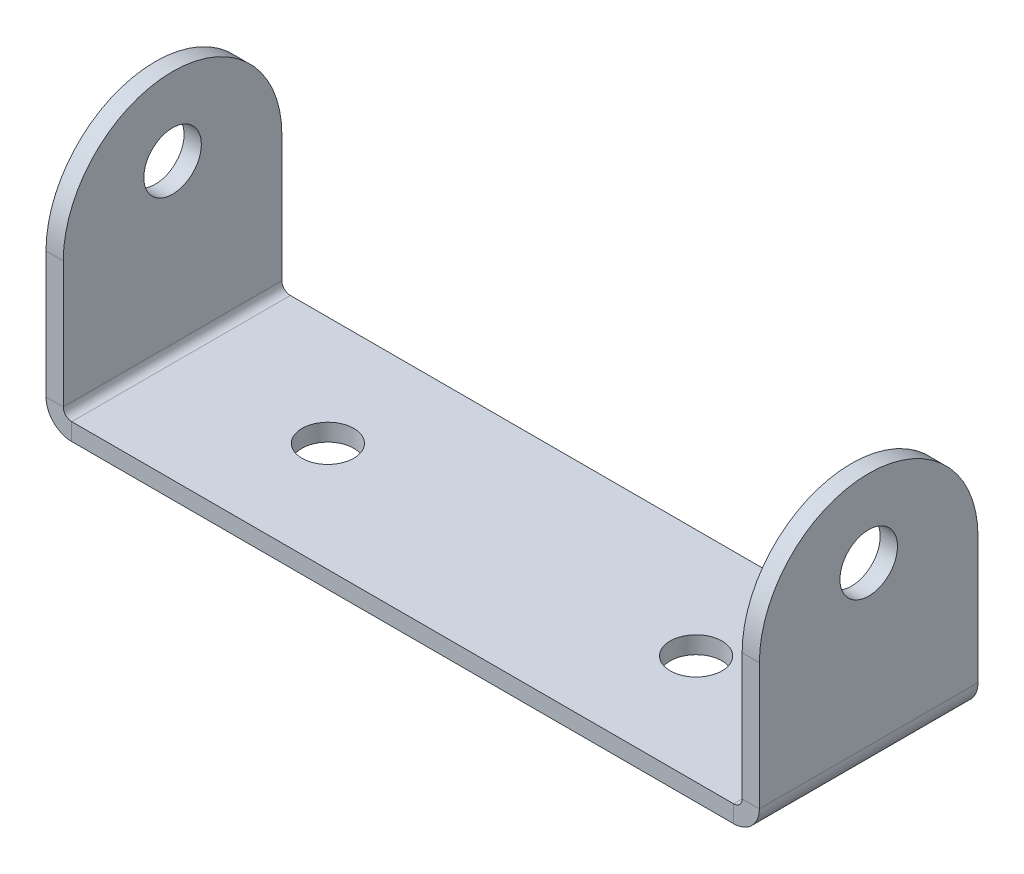
SolidWorks part; units mm, degrees
note: The reader was unsure of these and kept them because the rebuilt part matched: flange length of "Edge-Flange1", "Edge-Flange2".
ref_plane "Front Plane" through (0, 0, 0) normal (0, 0, 1) x (1, 0, 0)
ref_plane "Top Plane" through (0, 0, 0) normal (0, 1, 0) x (1, 0, 0)
ref_plane "Right Plane" through (0, 0, 0) normal (1, 0, 0) x (0, 0, -1)
sketch "Sketch1" plane through (0, 0, 0) normal (0, 1, 0) x (1, 0, 0)
  line L0 (0, 9.5) -> (15, 9.5) construction
  line L1 (0, 0) -> (62, 0)
  line L2 (0, 0) -> (0, 19)
  line L3 (0, 19) -> (62, 19)
  line L4 (62, 0) -> (62, 19)
  line L5 (62, 9.5) -> (47, 9.5) construction
  circle A0 centre (15, 9.5) radius 2.25
  circle A1 centre (47, 9.5) radius 2.25
  dimension "D5" = 4.5
  dimension "D6" = 4.5
  dimension "D1" = 19
  dimension "D2" = 62
  dimension "D3" = 15
  dimension "D4" = 15
base flange "Base-Flange1" sketch "Sketch1" thickness 1.5 reverse thickness direction no parameters "D1"=0.7366
edge flange "Edge-Flange1" sketch "Sketch8" flange angle 90 flange length 23 flange position material inside bend radius 0.7366 thickness 1.5 relief rectangular parameters "D6"=10
sketch "Sketch8" plane through (0, 0, 0) normal (-1, 0, 0) x (0, 0, 1)
  line L2 (-19, 0) -> (-19, 21.5)
  line L3 (-19, 21.5) -> (0, 21.5)
  line L4 (0, 21.5) -> (0, 0)
  line L7 (-19, 0) -> (0, 0) construction
  line L8 (-19, 0) -> (0, 0)
bend "EdgeBend1" bend radius 0.7366 bend angle 90 parameters "D5"=1
edge flange "Edge-Flange2" sketch "Sketch11" flange angle 90 flange length 23 flange position material inside bend radius 0.7366 thickness 1.5 relief rectangular parameters "D6"=10
sketch "Sketch11" plane through (62, 0, 0) normal (1, 0, 0) x (0, 0, -1)
  line L2 (0, 0) -> (0, 21.5)
  line L3 (0, 21.5) -> (19, 21.5)
  line L4 (19, 21.5) -> (19, 0)
  line L7 (0, 0) -> (19, 0) construction
  line L8 (0, 0) -> (19, 0)
bend "EdgeBend2" bend radius 0.7366 bend angle 90 parameters "D5"=2
sketch "Sketch12" plane through (62, 0, 0) normal (1, 0, 0) x (0, 0, -1)
  line L0 (9.5, 0.7366) -> (9.5, 11.7366) construction
  line L1 (19, 0.7366) -> (0, 0.7366) construction
  line L2 (0, 21.5) -> (0, 0.7366) construction
  line L3 (19, 0.7366) -> (19, 21.5) construction
  line L4 (0, 11.7366) -> (-3.0236, 11.7366)
  line L5 (-3.0236, 11.7366) -> (-3.0236, 23.5215)
  line L6 (-3.0236, 23.5215) -> (21.6636, 23.5215)
  line L7 (21.6636, 23.5215) -> (21.6636, 11.7366)
  line L8 (21.6636, 11.7366) -> (19, 11.7366)
  line L9 (9.5, 21.5) -> (9.5, 14.5) construction
  line L10 (19, 21.5) -> (0, 21.5) construction
  arc A0 (0, 11.7366) -> (19, 11.7366) centre (9.5, 11.7366) cw
  circle A2 centre (9.5, 14.5) radius 2.5
  dimension "D2" = 7
  dimension "D1" = 11
extrude "Cut-Extrude1" cut sketch "Sketch12" against normal through all normal cut yes
sketch "Bend-Lines1" [suppressed] plane through (0, 0, 0) normal (0, 1, 0) x (1, 0, 0)
sketch "Bounding-Box1" [suppressed] plane through (0, 0, 0) normal (0, 1, 0) x (1, 0, 0)
sheet metal parameters "Sheet-Metal1" thickness 1.5 parameters "D1"=0.7366
flat pattern "Flat-Pattern1" [suppressed]
sketch "Bend-Lines2" plane through (0, 0, 0) normal (0, 1, 0) x (1, 0, 0)
sketch3d "Bounding-Box2" [suppressed]
  line L0 (-62, 19, 0) -> (0, 19, 0) construction
  line L1 (-62, 0, 0) -> (0, 0, 0) construction
  line L2 (-62, 19, 0) -> (-62, 0, 0) construction
  line L3 (0, 19, 0) -> (0, 0, 0) construction
sheet metal parameters "Sheet-Metal2" thickness 1.5 parameters "D1"=0.7366
flat pattern "Flat-Pattern1"
sketch "Bend-Lines2" plane through (0, 0, 0) normal (0, 1, 0) x (1, 0, 0)
  line L0 (1.069, 19) -> (1.069, 0) construction
  line L1 (1.069, 19) -> (1.069, 0) construction
sketch3d "Bounding-Box2" [suppressed]
  line L0 (62, 19, 0) -> (-20.8619, 19, 0) construction
  line L1 (62, 0, 0) -> (-20.8619, 0, 0) construction
  line L2 (62, 19, 0) -> (62, 0, 0) construction
  line L3 (-20.8619, 19, 0) -> (-20.8619, 0, 0) construction
bend of the flat pattern "Flatten-<EdgeBend1>1"
sheet metal parameters "Sheet-Metal3" thickness 1.5 parameters "D1"=0.7366
flat pattern "Flat-Pattern1"
sketch "Bend-Lines2" plane through (0, 0, 0) normal (0, 1, 0) x (1, 0, 0)
  line L0 (1.069, 19) -> (1.069, 0) construction
  line L1 (1.069, 19) -> (1.069, 0) construction
  line L2 (60.931, 0) -> (60.931, 19) construction
  line L3 (60.931, 0) -> (60.931, 19) construction
sketch3d "Bounding-Box2" [suppressed]
  line L0 (82.8619, 19, 0) -> (-20.8619, 19, 0) construction
  line L1 (82.8619, 0, 0) -> (-20.8619, 0, 0) construction
  line L2 (82.8619, 19, 0) -> (82.8619, 0, 0) construction
  line L3 (-20.8619, 19, 0) -> (-20.8619, 0, 0) construction
bend of the flat pattern "Flatten-<EdgeBend1>1"
bend of the flat pattern "Flatten-<EdgeBend2>1"
sheet metal parameters "Sheet-Metal4" thickness 1.5 parameters "D1"=0.7366
flat pattern "Flat-Pattern1"
sketch "Bend-Lines2" plane through (0, 0, 0) normal (0, 1, 0) x (1, 0, 0)
  line L0 (1.069, 19) -> (1.069, 0) construction
  line L1 (1.069, 19) -> (1.069, 0) construction
  line L2 (60.931, 0) -> (60.931, 19) construction
  line L3 (60.931, 0) -> (60.931, 19) construction
sketch3d "Bounding-Box2" [suppressed]
  line L0 (82.5985, 19, 0) -> (-20.5985, 19, 0) construction
  line L1 (82.5985, 0, 0) -> (-20.5985, 0, 0) construction
  line L2 (82.5985, 19, 0) -> (82.5985, 0, 0) construction
  line L3 (-20.5985, 19, 0) -> (-20.5985, 0, 0) construction
bend of the flat pattern "Flatten-<EdgeBend1>1"
bend of the flat pattern "Flatten-<EdgeBend2>1"
